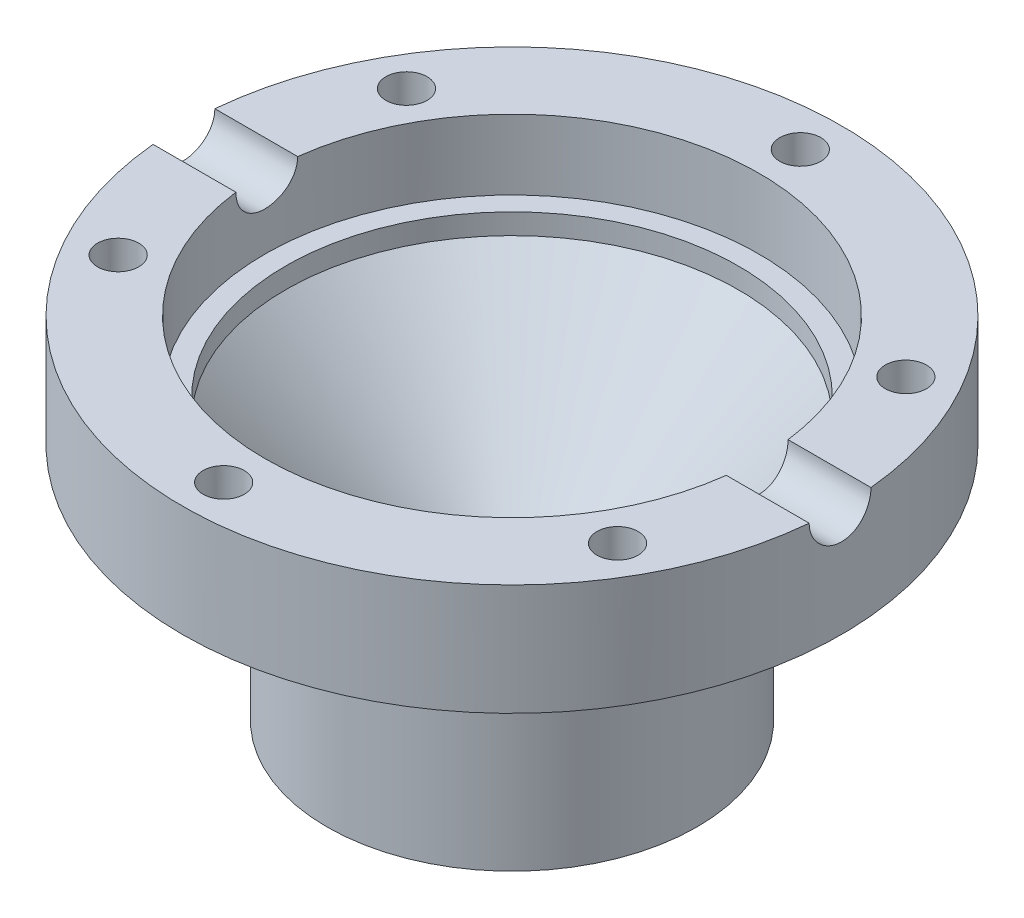
SolidWorks part; units mm, degrees
ref_plane "Front Plane" through (0, 0, 0) normal (0, 0, 1) x (1, 0, 0)
ref_plane "Top Plane" through (0, 0, 0) normal (0, 1, 0) x (1, 0, 0)
ref_plane "Right Plane" through (0, 0, 0) normal (1, 0, 0) x (0, 0, -1)
ref_axis "Centerline" through (0, 55, 0) along (0, -1, 0)
sketch "Sketch1" plane through (0, 0, 0) normal (0, 1, 0) x (1, 0, 0)
  circle A0 centre (0, 0) radius 20.32
  dimension "D1" = 40.64
extrude "Boss-Extrude1" add sketch "Sketch1" along normal blind 21.59
sketch "Sketch2" plane through (0, 0, 0) normal (0, 0, 1) x (1, 0, 0)
  line L0 (0, 26.2246) -> (0, -7.0612) construction
  line L5 (20.32, 21.59) -> (-20.32, 21.59) construction
  line L6 (0, 21.59) -> (-15.24, 21.59)
  line L7 (0, 21.59) -> (0, 17.272)
  line L8 (0, 17.272) -> (-15.24, 17.272)
  line L9 (-15.24, 21.59) -> (-15.24, 17.272)
  line L10 (-20.32, 21.59) -> (-20.32, 0) construction
  dimension "D1" = 5.08
  dimension "D2" = 4.318
revolve "Cut-Revolve1" cut sketch "Sketch2" angle 360 about axis through (0, 55, 0) along (0, -1, 0)
sketch "Sketch3" plane through (0, 0, 0) normal (0, 0, 1) x (1, 0, 0)
  line L0 (-20.32, 0) -> (20.32, 0) construction
  line L1 (-20.32, 14.732) -> (-15.24, 14.732)
  line L2 (-20.32, 14.732) -> (-20.32, 0)
  line L3 (-20.32, 0) -> (-15.24, 0)
  line L4 (-15.24, 14.732) -> (-15.24, 0)
  line L5 (20.32, 21.59) -> (-20.32, 21.59) construction
  line L6 (-20.32, 21.59) -> (-20.32, 0) construction
  dimension "D1" = 6.858
  dimension "D2" = 5.08
revolve "Cut-Revolve2" cut sketch "Sketch3" angle 360 about axis through (0, 55, 0) along (0, -1, 0)
sketch "Sketch4" plane through (0, 21.59, 0) normal (0, 1, 0) x (1, 0, 0)
  line L0 (0, 29.0947) -> (0, -35.1526) construction
  circle A0 centre (0, 17.78) radius 1.27
  dimension "D1" = 2.54
  dimension "D2" = 17.78
extrude "Cut-Extrude1" cut sketch "Sketch4" against normal up to next
pattern_circular "CirPattern1" count 6 over 360 about axis through (0, 55, 0) along (0, -1, 0) of "Cut-Extrude1"
sketch "Sketch5" plane through (0, 0, 0) normal (0, -1, 0) x (1, 0, 0)
  circle A0 centre (0, 0) radius 4.699
  dimension "D1" = 9.398
extrude "Cut-Extrude2" cut sketch "Sketch5" against normal up to next
sketch "Sketch7" plane through (0, 0, 0) normal (0, 0, 1) x (1, 0, 0)
  line L0 (-19.3213, 14.732) -> (23.1214, 14.732) construction
  line L1 (-20.32, 14.732) -> (20.32, 14.732) construction
  line L2 (-15.24, 14.732) -> (-15.24, 25.6293) construction
  line L4 (-15.24, 14.732) -> (-11.4097, 10.9017)
  line L5 (-11.4097, 10.9017) -> (-11.4097, 0)
  line L6 (-15.24, 0) -> (15.24, 0) construction
  line L7 (-11.4097, 0) -> (-15.24, 0)
  line L9 (-15.24, 14.732) -> (-15.24, 0)
  dimension "D1" = 45
  dimension "D2" = 10.9017
revolve "Cut-Revolve3" cut sketch "Sketch7" angle 360 about axis through (0, 55, 0) along (0, -1, 0)
sketch "Sketch8" plane through (0, 0, 0) normal (0, 0, 1) x (1, 0, 0)
  line L0 (-4.699, 24.8968) -> (-4.699, 18.7411) construction
  line L1 (-15.24, 24.5608) -> (-15.24, -3.2139) construction
  line L2 (15.24, 17.272) -> (-15.24, 17.272) construction
  line L3 (-4.699, 17.272) -> (-13.97, 17.272)
  line L4 (-13.97, 16.002) -> (-4.699, 6.731)
  line L5 (-22.2629, 0) -> (17.7783, 0) construction
  line L6 (-4.699, 6.731) -> (-4.699, 17.272)
  line L7 (-4.699, 17.272) -> (-4.699, -4.4972) construction
  line L8 (-13.97, 17.272) -> (-13.97, 16.002)
  line L9 (-13.97, 16.002) -> (-15.24, 17.272) construction
  line L10 (-15.24, 17.272) -> (-13.97, 17.272) construction
  dimension "D1" = 4.699
  dimension "D2" = 15.24
  dimension "D3" = 45
  dimension "D4" = 1.27
revolve "Cut-Revolve4" cut sketch "Sketch8" angle 360 about axis through (0, 55, 0) along (0, -1, 0)
ref_plane "Inlet Plane" through (20.32, 0, 0) normal (1, 0, 0) x (0, 0, -1)
sketch "Sketch9" plane through (20.32, 0, 0) normal (1, 0, 0) x (0, 0, -1)
  line L0 (0, 25.9244) -> (0, -6.8119) construction
  line L1 (20.32, 21.59) -> (-20.32, 21.59) construction
  circle A0 centre (0, 21.59) radius 1.905
  dimension "D1" = 3.81
extrude "Cut-Extrude3" cut sketch "Sketch9" against normal through all
